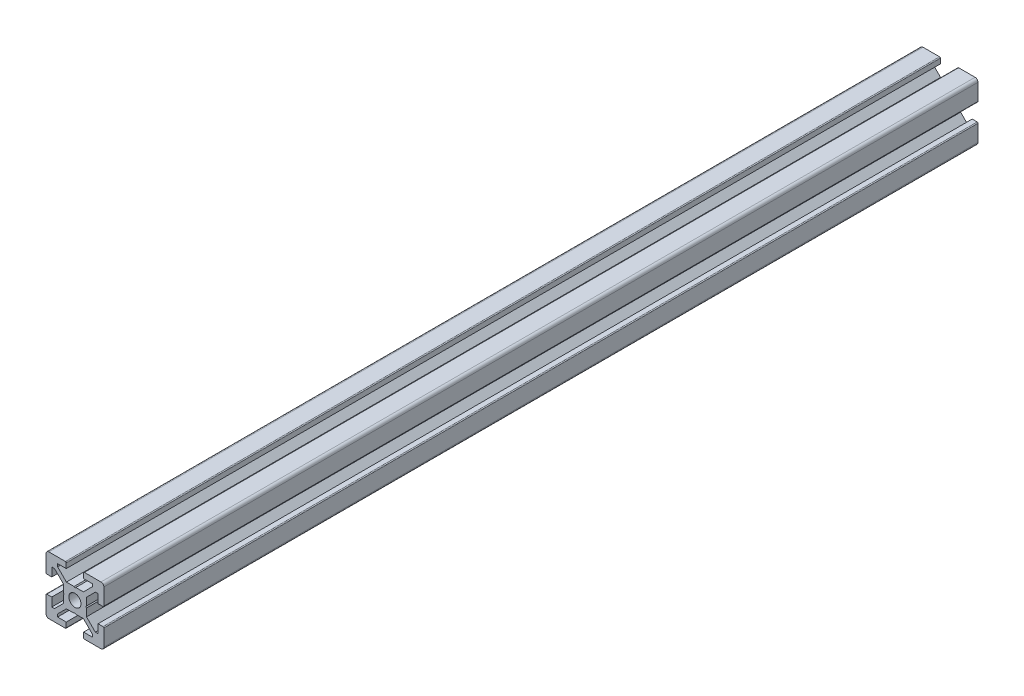
SolidWorks part; units mm, degrees
ref_plane "Front Plane" through (0, 0, 0) normal (0, 0, 1) x (1, 0, 0)
ref_plane "Top Plane" through (0, 0, 0) normal (0, 1, 0) x (1, 0, 0)
ref_plane "Right Plane" through (0, 0, 0) normal (1, 0, 0) x (0, 0, -1)
sketch "Sketch1" plane through (0, 0, 0) normal (0, 0, -1) x (-1, 0, 0)
  line L0 (10, 3.3) -> (10, 9)
  line L1 (9, 10) -> (3.3, 10)
  line L2 (3, 9.7) -> (3, 8)
  line L3 (3, 8) -> (6, 8)
  line L4 (6, 8) -> (6, 7.0607)
  line L5 (6, 7.0607) -> (2.9393, 4)
  line L6 (2.9393, 4) -> (0.3, 4)
  line L7 (0.3, 4) -> (0, 3.7)
  line L8 (0, 3.7) -> (-0.3, 4)
  line L9 (-0.3, 4) -> (-2.9393, 4)
  line L10 (-2.9393, 4) -> (-6, 7.0607)
  line L11 (-6, 7.0607) -> (-6, 8)
  line L12 (-6, 8) -> (-3, 8)
  line L13 (-3, 8) -> (-3, 9.7)
  line L14 (-3.3, 10) -> (-9, 10)
  line L15 (-10, 9) -> (-10, 3.3)
  line L16 (-9.7, 3) -> (-8, 3)
  line L17 (-8, 3) -> (-8, 6)
  line L18 (-8, 6) -> (-7.0607, 6)
  line L19 (-7.0607, 6) -> (-4, 2.9393)
  line L20 (-4, 2.9393) -> (-4, 0.3)
  line L21 (-4, 0.3) -> (-3.7, 0)
  line L22 (-3.7, 0) -> (-4, -0.3)
  line L23 (-4, -0.3) -> (-4, -2.9393)
  line L24 (-4, -2.9393) -> (-7.0607, -6)
  line L25 (-7.0607, -6) -> (-8, -6)
  line L26 (-8, -6) -> (-8, -3)
  line L27 (-8, -3) -> (-9.7, -3)
  line L28 (-10, -3.3) -> (-10, -9)
  line L29 (-9, -10) -> (-3.3, -10)
  line L30 (-3, -9.7) -> (-3, -8)
  line L31 (-3, -8) -> (-6, -8)
  line L32 (-6, -8) -> (-6, -7.0607)
  line L33 (-6, -7.0607) -> (-2.9393, -4)
  line L34 (-2.9393, -4) -> (-0.3, -4)
  line L35 (-0.3, -4) -> (0, -3.7)
  line L36 (0, -3.7) -> (0.3, -4)
  line L37 (0.3, -4) -> (2.9393, -4)
  line L38 (2.9393, -4) -> (6, -7.0607)
  line L39 (6, -7.0607) -> (6, -8)
  line L40 (6, -8) -> (3, -8)
  line L41 (3, -8) -> (3, -9.7)
  line L42 (3.3, -10) -> (9, -10)
  line L43 (10, -9) -> (10, -3.3)
  line L44 (9.7, -3) -> (8, -3)
  line L45 (8, -3) -> (8, -6)
  line L46 (8, -6) -> (7.0607, -6)
  line L47 (7.0607, -6) -> (4, -2.9393)
  line L48 (4, -2.9393) -> (4, -0.3)
  line L49 (4, -0.3) -> (3.7, 0)
  line L50 (3.7, 0) -> (4, 0.3)
  line L51 (4, 0.3) -> (4, 2.9393)
  line L52 (4, 2.9393) -> (7.0607, 6)
  line L53 (7.0607, 6) -> (8, 6)
  line L54 (8, 6) -> (8, 3)
  line L55 (8, 3) -> (9.7, 3)
  line L56 (9, -9) -> (-9, 9) construction
  line L57 (-9, -9) -> (9, 9) construction
  line L58 (-3.7, 0) -> (3.7, 0) construction
  line L59 (0, -3.7) -> (0, 3.7) construction
  circle A0 centre (0, 0) radius 2.1
  arc A1 (10, 9) -> (9, 10) centre (9, 9) ccw
  arc A2 (3.3, 10) -> (3, 9.7) centre (3.3, 9.7) ccw
  arc A3 (-3, 9.7) -> (-3.3, 10) centre (-3.3, 9.7) ccw
  arc A4 (-9, 10) -> (-10, 9) centre (-9, 9) ccw
  arc A5 (-10, 3.3) -> (-9.7, 3) centre (-9.7, 3.3) ccw
  arc A6 (-9.7, -3) -> (-10, -3.3) centre (-9.7, -3.3) ccw
  arc A7 (-10, -9) -> (-9, -10) centre (-9, -9) ccw
  arc A8 (-3.3, -10) -> (-3, -9.7) centre (-3.3, -9.7) ccw
  arc A9 (3, -9.7) -> (3.3, -10) centre (3.3, -9.7) ccw
  arc A10 (9, -10) -> (10, -9) centre (9, -9) ccw
  arc A11 (10, -3.3) -> (9.7, -3) centre (9.7, -3.3) ccw
  arc A12 (9.7, 3) -> (10, 3.3) centre (9.7, 3.3) ccw
  point P83 (0, 0)
  point P85 (0, 0)
  point P86 (0, 0)
  dimension "D1" = 1
  dimension "D4" = 0.3
  dimension "D10" = 4.2
  dimension "D2" = 20
  dimension "D3" = 6
  dimension "D5" = 3
  dimension "D6" = 1.7
  dimension "D7" = 0.9393
  dimension "D8" = 0.6
  dimension "D9" = 4
  dimension "D11" = 3.0607
  dimension "D12" = 3.0607
  dimension "D13" = 3.0607
  dimension "D14" = 5.7
  dimension "D15" = 5.7
  dimension "D16" = 0.9393
  dimension "D17" = 0.9393
  dimension "D18" = 3.0607
extrude "Boss-Extrude1" add sketch "Sketch1" against normal mid plane 302.2
ref_axis "Axis1" through (0, 0, 151.1) along (0, 0, -1)
